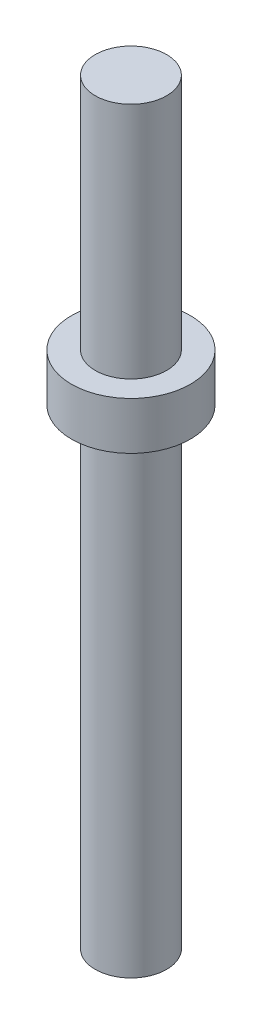
SolidWorks part; units mm, degrees
ref_plane "Front Plane" through (0, 0, 0) normal (0, 0, 1) x (1, 0, 0)
ref_plane "Top Plane" through (0, 0, 0) normal (0, 1, 0) x (1, 0, 0)
ref_plane "Right Plane" through (0, 0, 0) normal (1, 0, 0) x (0, 0, -1)
sketch "Sketch1" plane through (0, 0, 0) normal (0, 1, 0) x (1, 0, 0)
  circle A0 centre (0, 0) radius 1.5
  dimension "D1" = 3
extrude "Boss-Extrude1" add sketch "Sketch1" along normal blind 19.8
sketch "Sketch2" plane through (0, 19.8, 0) normal (0, 1, 0) x (1, 0, 0)
  circle A0 centre (0, 0) radius 2.5
extrude "Boss-Extrude2" add sketch "Sketch2" along normal blind 2
sketch "Sketch3" plane through (0, 21.8, 0) normal (0, 1, 0) x (1, 0, 0)
  circle A0 centre (0, 0) radius 1.5
extrude "Boss-Extrude3" add sketch "Sketch3" along normal blind 10
equation "\"D1@Boss-Extrude1\"=21.8-\"D1@Boss-Extrude2\""
